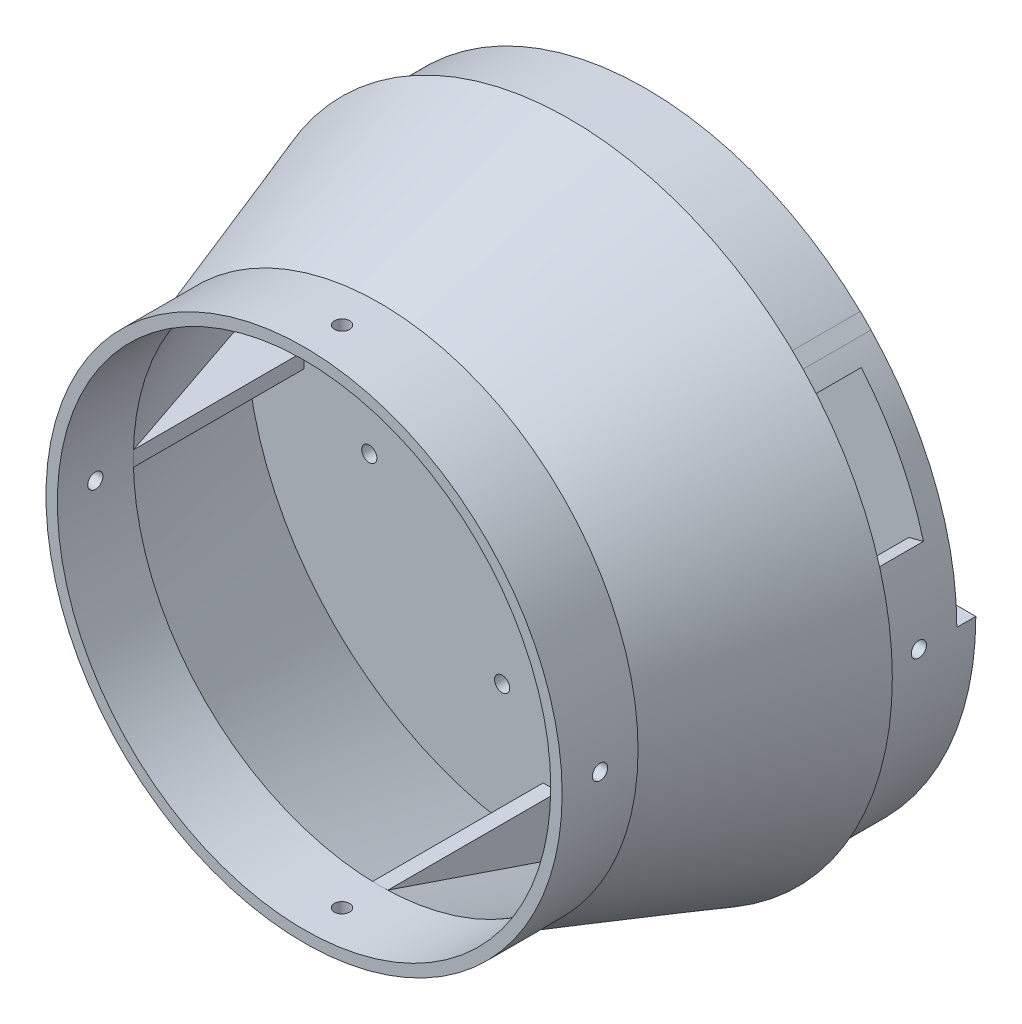
SolidWorks part; units mm, degrees
ref_plane "Front Plane" through (0, 0, 0) normal (0, 0, 1) x (1, 0, 0)
ref_plane "Top Plane" through (0, 0, 0) normal (0, 1, 0) x (1, 0, 0)
ref_plane "Right Plane" through (0, 0, 0) normal (1, 0, 0) x (0, 0, -1)
sketch "Sketch10" plane through (0, 0, 0) normal (0, 1, 0) x (1, 0, 0)
  line L9 (68, 0) -> (85, 50)
  line L10 (65, 0) -> (65, -20)
  line L11 (65, -20) -> (68, -20)
  line L12 (68, -20) -> (68, 0)
  line L13 (85, 50) -> (0, 50)
  line L14 (0, 50) -> (0, 45)
  line L16 (0, 0) -> (0, 90.5218) construction
  line L17 (65, 0) -> (80.3, 45)
  line L18 (0, 45) -> (80.3, 45)
  dimension "D1" = 65
  dimension "D2" = 20
  dimension "D3" = 50
  dimension "D4" = 85
  dimension "D5" = 68
  dimension "D6" = 5
revolve "Revolve2" add sketch "Sketch10" angle 360 about L16
sketch "Sketch12" plane through (0, 0, 0) normal (0, 1, 0) x (1, 0, 0)
  line L4 (-80.3, 45) -> (-65, 0)
  line L5 (-65, 0) -> (-65, 45)
  line L6 (-80.3, 45) -> (80.3, 45) construction
  line L7 (-65, 45) -> (-80.3, 45)
extrude "Boss-Extrude5" add sketch "Sketch12" along normal blind 2 and the other way blind 2
pattern_circular "CirPattern3" count 4 every 90 about axis through (0, 0, -50) along (0, 0, 1) of "Boss-Extrude5"
sketch "Sketch13" plane through (0, 0, -50) normal (0, 0, -1) x (-1, 0, 0)
  arc A0 (70, 42.7083) -> (70, -42.7083) centre (0, 0) ccw
  arc A1 (70, 34.4093) -> (70, -34.4093) centre (0, 0) ccw
  circle A2 centre (0, 0) radius 82 construction
  circle A3 centre (0, 0) radius 78 construction
  circle A4 centre (0, 0) radius 82
  circle A5 centre (0, 0) radius 78
  dimension "D1" = 164
  dimension "D2" = 4
extrude "Boss-Extrude6" add sketch "Sketch13" along normal blind 20 contours A0 A4 A5 A1 region at (-76.7102, 21.5537, -50)
sketch "Sketch14" plane through (0, 0, 0) normal (0, 1, 0) x (1, 0, 0)
  line L0 (-65, -20) -> (65, -20) construction
  circle A0 centre (0, -10) radius 2
  dimension "D1" = 4
  dimension "D2" = 10
extrude "Cut-Extrude1" cut sketch "Sketch14" against normal blind 95
pattern_circular "CirPattern4" count 4 every 90 about axis through (0, 0, 20) along (0, 0, 1) of "Cut-Extrude1"
fillet "Fillet1" radius 5 1 edges at (-78, 0, -50)
sketch "Sketch16" plane through (0, 0, 0) normal (0, 1, 0) x (1, 0, 0)
  line L0 (85, 50) -> (-85, 50) construction
  circle A0 centre (0, 60) radius 2
  dimension "D1" = 4
  dimension "D2" = 10
extrude "Cut-Extrude2" cut sketch "Sketch16" against normal blind 94
pattern_circular "CirPattern5" count 2 every 90 about axis through (0, 0, -70) along (0, 0, -1) of "Cut-Extrude2" other way count 2
sketch "Sketch17" plane through (0, 0, -50) normal (0, 0, -1) x (-1, 0, 0)
  line L0 (0, 0) -> (-47.8133, 12.8115) construction
  line L1 (0, 0) -> (-12.8115, 47.8133) construction
  circle A0 centre (-47.8133, 12.8115) radius 2
  circle A4 centre (-12.8115, 47.8133) radius 2
  circle A5 centre (12.8115, -47.8133) radius 2
  circle A6 centre (47.8133, -12.8115) radius 2
  point P12 (0, 0)
  point P16 (0, 0)
  dimension "D1" = 4
  dimension "D2" = 49.5
  dimension "D4" = 60
  dimension "D3" = 2
  dimension "D5" = 2
extrude "Cut-Extrude4" cut sketch "Sketch17" against normal blind 900
sketch "Sketch19" plane through (0, 0, -70) normal (0, 0, -1) x (-1, 0, 0)
  line L0 (0, 0) -> (0, 85) construction
  line L1 (0, 0) -> (-79.2059, 21.2232)
  line L6 (0, 0) -> (-62.8156, 52.7086)
  circle A0 centre (0, 0) radius 85 construction
  arc A2 (-62.8156, 52.7086) -> (-79.2059, 21.2232) centre (0, 0) ccw
  dimension "D1" = 75
  dimension "D2" = 50
extrude "Cut-Extrude7" cut sketch "Sketch19" against normal blind 20
mirror "Mirror1" about plane through (0, 0, 0) normal (1, 0, 0) of "Cut-Extrude7"
sketch "Sketch22" plane through (0, 0, -70) normal (0, 0, -1) x (-1, 0, 0)
  circle A2 centre (0, 0) radius 82
  circle A3 centre (0, 0) radius 60
  arc M2 (-59.7515, 50.1374) -> (59.7515, 50.1374) centre (0, 0) cw
  line M3 (59.7515, 50.1374) -> (62.8156, 52.7086)
  arc M4 (62.8156, 52.7086) -> (-62.8156, 52.7086) centre (0, 0) ccw
  line M5 (-62.8156, 52.7086) -> (-59.7515, 50.1374)
  dimension "D1" = 120
extrude "Boss-Extrude8" add sketch "Sketch22" against normal blind 6 contours A2 A3 M5 M3 M2 | M5 M2 M3 M4 region at (27.262, -74.9018, -70) region at (-60.4504, 52.4159, -70)
sketch "Sketch24" plane through (0, 0, -50) normal (0, 0, -1) x (-1, 0, 0)
  circle A0 centre (0, 0) radius 25
  dimension "D1" = 50
extrude "Cut-Extrude8" cut sketch "Sketch24" against normal blind 5
ref_plane "Plane1" through (0, 0, 0) normal (-0.7071, 0.7071, 0) x (0.7071, 0.7071, 0)
sketch "Sketch28" plane through (0, 0, 0) normal (-0.7071, 0.7071, 0) x (0.7071, 0.7071, 0)
  line L0 (-68, 50) -> (-68, 70)
  line L1 (82, 70) -> (-82, 70) construction
  line L2 (-68, 70) -> (-82, 70)
  line L3 (-82, 70) -> (-82, 50)
  line L4 (85, 50) -> (-85, 50) construction
  line L5 (-82, 70) -> (-82, 50) construction
  line L6 (-82, 50) -> (-68, 50)
extrude "Boss-Extrude9" add sketch "Sketch28" along normal blind 2 and the other way blind 2
pattern_circular "CirPattern6" count 4 every 90 about axis through (0, 0, -70) along (0, 0, -1) of "Boss-Extrude9"
sketch "Sketch29" plane through (0, 0, -70) normal (0, 0, -1) x (-1, 0, 0)
  line L2 (79.2059, 21.2232) -> (75.8252, 20.3173)
  line L6 (-75, 0) -> (-82, 0)
  line L7 (75, 0) -> (75.8252, 20.3173)
  arc A0 (-82, 0) -> (79.2059, 21.2232) centre (0, 0) ccw
  arc A2 (-75, 0) -> (75, 0) centre (0, 0) ccw
  dimension "D3" = 150
extrude "Boss-Extrude10" add sketch "Sketch29" along normal blind 5 contours A0 L2 L7 A2 L6
